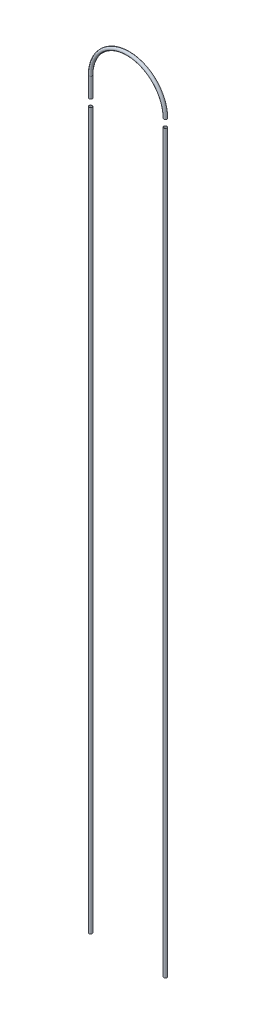
SolidWorks part; units mm, degrees
ref_plane "Front Plane" through (0, 0, 0) normal (0, 0, 1) x (1, 0, 0)
ref_plane "Top Plane" through (0, 0, 0) normal (0, 1, 0) x (1, 0, 0)
ref_plane "Right Plane" through (0, 0, 0) normal (1, 0, 0) x (0, 0, -1)
sketch3d "3DSketch1"
  line L0 (-21659.4014, -2258.4694, 40208.3753) -> (-21659.4014, -2253.4694, 40208.3753) construction
  line L1 (-21659.4014, -2253.4694, 40208.3753) -> (-21659.4014, 11528.5306, 40208.3753)
  line L2 (-21659.4014, 11528.5306, 40208.3753) -> (-23039.4014, 11528.5306, 40208.3753) construction
  line L3 (-22349.4014, 11528.5306, 40208.3753) -> (-22349.4014, 12218.5306, 40208.3753) construction
  line L4 (-23039.4014, 11528.5306, 40208.3753) -> (-23039.4014, 11163.1904, 40208.3753)
  line L5 (-22911.2904, 11163.1904, 40109.5295) -> (-22911.2904, 11163.1904, 40208.3753) construction
  line L6 (-22911.2904, 12362.1915, 40109.5295) -> (-22911.2904, -2637.8085, 40109.5295) construction
  line L7 (-22911.2904, 11163.1904, 40208.3753) -> (-23039.4014, 11163.1904, 40208.3753) construction
  arc A1 (-23039.4014, 11528.5306, 40208.3753) -> (-21659.4014, 11528.5306, 40208.3753) centre (-22349.4014, 11528.5306, 40208.3753) cw
  point P10 (-22349.4014, 11528.5306, 39518.3753)
  dimension "D1" = 690
  dimension "D2" = 128.111
  dimension "D3" = 110
sweep "Sweep-Thin1" add path "3DSketch1" circular profile diameter 60 parameters "D1"=3, "D3"=60
sketch3d "3DSketch2"
  line L0 (-23039.4014, 7382.62, 40208.3753) -> (-22077.787, 6420.8653, 40224.8051)
  line L1 (-23039.4014, 11163.1904, 40208.3753) -> (-23039.4014, 11528.5306, 40208.3753) construction
  line L2 (-23039.4014, 7382.62, 40208.3753) -> (-23039.4014, 6971.5252, 40208.3753) construction
  circle A0 centre (-22077.787, 6420.8653, 40224.8051) radius 26.09 construction
  point P8 (-22059.3393, 6402.4169, 40224.6406)
  dimension "D1" = 45
sweep "Sweep-Thin2" [suppressed] add path "3DSketch2" circular profile diameter 60 parameters "D1"=3, "D3"=60
sketch3d "3DSketch3"
  line L0 (-21659.4014, 11528.5306, 40208.3753) -> (-21659.4014, 11384.9457, 40208.3753) construction
  line L1 (-21659.4014, 11384.9457, 40208.3753) -> (-21659.4014, -2185.0543, 40208.3753)
  circle A0 centre (-21659.4014, 11528.5306, 40208.3753) radius 27 construction
  point P4 (-21659.4014, 11555.5306, 40208.3753)
sweep "Sweep-Thin3" add path "3DSketch3" circular profile diameter 60 parameters "D1"=3, "D3"=60
sketch3d "3DSketch4"
  line L0 (-23039.4014, 11253.1313, 40208.3753) -> (-23039.4014, 11026.3486, 40208.3753) construction
  line L1 (-23039.4014, 11026.3486, 40208.3753) -> (-23039.4014, -2173.6514, 40208.3753)
  circle A0 centre (-23039.4014, 11253.1313, 40208.3753) radius 26.2509 construction
  point P4 (-23039.4014, 11226.8804, 40208.3753)
sweep "Sweep-Thin4" add path "3DSketch4" circular profile diameter 60 parameters "D1"=3, "D3"=60
